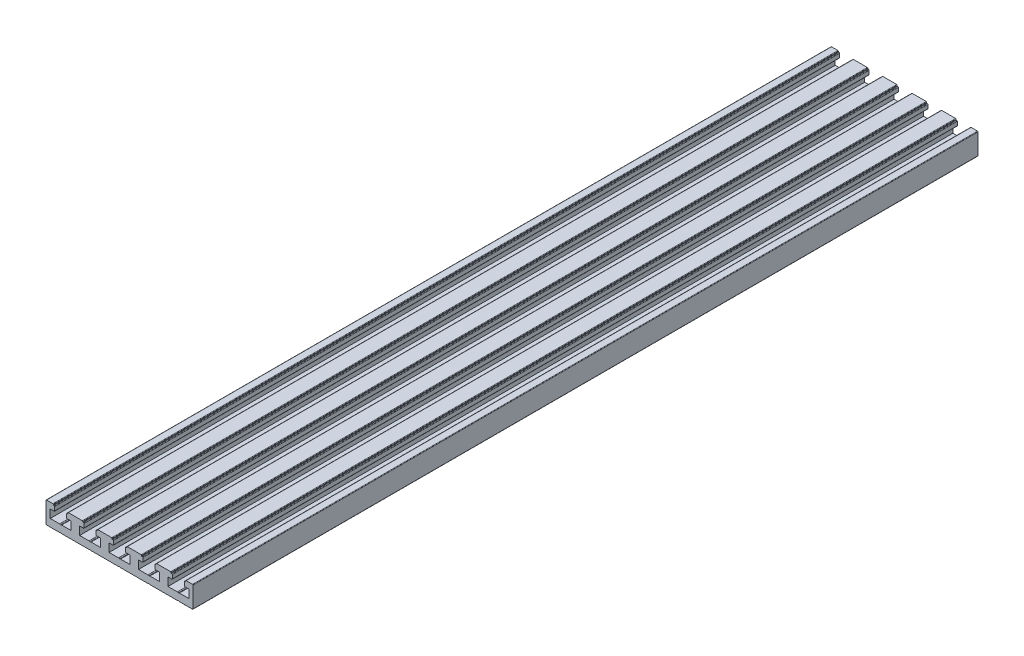
SolidWorks part; units mm, degrees
material "6061-T6 (SS)"
ref_plane "Front Plane" through (0, 0, 0) normal (0, 0, 1) x (1, 0, 0)
ref_plane "Top Plane" through (0, 0, 0) normal (0, 1, 0) x (1, 0, 0)
ref_plane "Right Plane" through (0, 0, 0) normal (1, 0, 0) x (0, 0, -1)
sketch "Sketch1" plane through (0, 0, 0) normal (0, 0, -1) x (-1, 0, 0)
  line L0 (0, 1.72) -> (0, -1.72) construction
  line L1 (-37.45, 8.85) -> (-37.45, -1.65)
  line L2 (-37.2, -1.9) -> (-30.5436, -1.9)
  line L3 (-30.4589, -1.8852) -> (-30, -1.72)
  line L4 (-30, -1.72) -> (-29.5411, -1.8852)
  line L5 (-29.4564, -1.9) -> (-15.5436, -1.9)
  line L6 (-15.4589, -1.8852) -> (-15, -1.72)
  line L7 (-15, -1.72) -> (-14.5411, -1.8852)
  line L8 (-14.4564, -1.9) -> (-0.5436, -1.9)
  line L9 (-0.4589, -1.8852) -> (0, -1.72)
  line L10 (0, -1.72) -> (0.4589, -1.8852)
  line L11 (0.5436, -1.9) -> (14.4564, -1.9)
  line L12 (14.5411, -1.8852) -> (15, -1.72)
  line L13 (15, -1.72) -> (15.4589, -1.8852)
  line L14 (15.5436, -1.9) -> (29.4564, -1.9)
  line L15 (29.5411, -1.8852) -> (30, -1.72)
  line L16 (30, -1.72) -> (30.4589, -1.8852)
  line L17 (30.5436, -1.9) -> (37.2, -1.9)
  line L18 (37.45, -1.65) -> (37.45, 8.85)
  line L19 (37.2, 9.1) -> (33.95, 9.1)
  line L20 (33.7, 8.85) -> (33.7, 8.5)
  line L21 (33.7, 8.5) -> (33.32, 8.5)
  line L22 (33.07, 8.25) -> (33.07, 6.35)
  line L23 (33.32, 6.1) -> (35.3, 6.1)
  line L24 (35.3, 6.1) -> (35.3, 1.9)
  line L25 (35.3, 1.9) -> (30.5436, 1.9)
  line L26 (30.4589, 1.8852) -> (30, 1.72)
  line L27 (30, 1.72) -> (29.5411, 1.8852)
  line L28 (29.4564, 1.9) -> (24.7, 1.9)
  line L29 (24.7, 1.9) -> (24.7, 6.1)
  line L30 (24.7, 6.1) -> (26.68, 6.1)
  line L31 (26.93, 6.35) -> (26.93, 8.25)
  line L32 (26.68, 8.5) -> (26.3, 8.5)
  line L33 (26.3, 8.5) -> (26.3, 8.85)
  line L34 (26.05, 9.1) -> (18.95, 9.1)
  line L35 (18.7, 8.85) -> (18.7, 8.5)
  line L36 (18.7, 8.5) -> (18.32, 8.5)
  line L37 (18.07, 8.25) -> (18.07, 6.35)
  line L38 (18.32, 6.1) -> (20.3, 6.1)
  line L39 (20.3, 6.1) -> (20.3, 1.9)
  line L40 (20.3, 1.9) -> (15.5436, 1.9)
  line L41 (15.4589, 1.8852) -> (15, 1.72)
  line L42 (15, 1.72) -> (14.5411, 1.8852)
  line L43 (14.4564, 1.9) -> (9.7, 1.9)
  line L44 (9.7, 1.9) -> (9.7, 6.1)
  line L45 (9.7, 6.1) -> (11.68, 6.1)
  line L46 (11.93, 6.35) -> (11.93, 8.25)
  line L47 (11.68, 8.5) -> (11.3, 8.5)
  line L48 (11.3, 8.5) -> (11.3, 8.85)
  line L49 (11.05, 9.1) -> (3.95, 9.1)
  line L50 (3.7, 8.85) -> (3.7, 8.5)
  line L51 (3.7, 8.5) -> (3.32, 8.5)
  line L52 (3.07, 8.25) -> (3.07, 6.35)
  line L53 (3.32, 6.1) -> (5.3, 6.1)
  line L54 (5.3, 6.1) -> (5.3, 1.9)
  line L55 (5.3, 1.9) -> (0.5436, 1.9)
  line L56 (0.4589, 1.8852) -> (0, 1.72)
  line L57 (0, 1.72) -> (-0.4589, 1.8852)
  line L58 (-0.5436, 1.9) -> (-5.3, 1.9)
  line L59 (-5.3, 1.9) -> (-5.3, 6.1)
  line L60 (-5.3, 6.1) -> (-3.32, 6.1)
  line L61 (-3.07, 6.35) -> (-3.07, 8.25)
  line L62 (-3.32, 8.5) -> (-3.7, 8.5)
  line L63 (-3.7, 8.5) -> (-3.7, 8.85)
  line L64 (-3.95, 9.1) -> (-11.05, 9.1)
  line L65 (-11.3, 8.85) -> (-11.3, 8.5)
  line L66 (-11.3, 8.5) -> (-11.68, 8.5)
  line L67 (-11.93, 8.25) -> (-11.93, 6.35)
  line L68 (-11.68, 6.1) -> (-9.7, 6.1)
  line L69 (-9.7, 6.1) -> (-9.7, 1.9)
  line L70 (-9.7, 1.9) -> (-14.4564, 1.9)
  line L71 (-14.5411, 1.8852) -> (-15, 1.72)
  line L72 (-15, 1.72) -> (-15.4589, 1.8852)
  line L73 (-15.5436, 1.9) -> (-20.3, 1.9)
  line L74 (-20.3, 1.9) -> (-20.3, 6.1)
  line L75 (-20.3, 6.1) -> (-18.32, 6.1)
  line L76 (-18.07, 6.35) -> (-18.07, 8.25)
  line L77 (-18.32, 8.5) -> (-18.7, 8.5)
  line L78 (-18.7, 8.5) -> (-18.7, 8.85)
  line L79 (-18.95, 9.1) -> (-26.05, 9.1)
  line L80 (-26.3, 8.85) -> (-26.3, 8.5)
  line L81 (-26.3, 8.5) -> (-26.68, 8.5)
  line L82 (-26.93, 8.25) -> (-26.93, 6.35)
  line L83 (-26.68, 6.1) -> (-24.7, 6.1)
  line L84 (-24.7, 6.1) -> (-24.7, 1.9)
  line L85 (-24.7, 1.9) -> (-29.4564, 1.9)
  line L86 (-29.5411, 1.8852) -> (-30, 1.72)
  line L87 (-30, 1.72) -> (-30.4589, 1.8852)
  line L88 (-30.5436, 1.9) -> (-35.3, 1.9)
  line L89 (-35.3, 1.9) -> (-35.3, 6.1)
  line L90 (-35.3, 6.1) -> (-33.32, 6.1)
  line L91 (-33.07, 6.35) -> (-33.07, 8.25)
  line L92 (-33.32, 8.5) -> (-33.7, 8.5)
  line L93 (-33.7, 8.5) -> (-33.7, 8.85)
  line L94 (-33.95, 9.1) -> (-37.2, 9.1)
  arc A0 (-37.45, -1.65) -> (-37.2, -1.9) centre (-37.2, -1.65) ccw
  arc A1 (-30.5436, -1.9) -> (-30.4589, -1.8852) centre (-30.5436, -1.65) ccw
  arc A2 (-29.5411, -1.8852) -> (-29.4564, -1.9) centre (-29.4564, -1.65) ccw
  arc A3 (-15.5436, -1.9) -> (-15.4589, -1.8852) centre (-15.5436, -1.65) ccw
  arc A4 (-14.5411, -1.8852) -> (-14.4564, -1.9) centre (-14.4564, -1.65) ccw
  arc A5 (-0.5436, -1.9) -> (-0.4589, -1.8852) centre (-0.5436, -1.65) ccw
  arc A6 (0.4589, -1.8852) -> (0.5436, -1.9) centre (0.5436, -1.65) ccw
  arc A7 (14.4564, -1.9) -> (14.5411, -1.8852) centre (14.4564, -1.65) ccw
  arc A8 (15.4589, -1.8852) -> (15.5436, -1.9) centre (15.5436, -1.65) ccw
  arc A9 (29.4564, -1.9) -> (29.5411, -1.8852) centre (29.4564, -1.65) ccw
  arc A10 (30.4589, -1.8852) -> (30.5436, -1.9) centre (30.5436, -1.65) ccw
  arc A11 (37.2, -1.9) -> (37.45, -1.65) centre (37.2, -1.65) ccw
  arc A12 (37.45, 8.85) -> (37.2, 9.1) centre (37.2, 8.85) ccw
  arc A13 (33.95, 9.1) -> (33.7, 8.85) centre (33.95, 8.85) ccw
  arc A14 (33.32, 8.5) -> (33.07, 8.25) centre (33.32, 8.25) ccw
  arc A15 (33.07, 6.35) -> (33.32, 6.1) centre (33.32, 6.35) ccw
  arc A16 (30.5436, 1.9) -> (30.4589, 1.8852) centre (30.5436, 1.65) ccw
  arc A17 (29.5411, 1.8852) -> (29.4564, 1.9) centre (29.4564, 1.65) ccw
  arc A18 (26.68, 6.1) -> (26.93, 6.35) centre (26.68, 6.35) ccw
  arc A19 (26.93, 8.25) -> (26.68, 8.5) centre (26.68, 8.25) ccw
  arc A20 (26.3, 8.85) -> (26.05, 9.1) centre (26.05, 8.85) ccw
  arc A21 (18.95, 9.1) -> (18.7, 8.85) centre (18.95, 8.85) ccw
  arc A22 (18.32, 8.5) -> (18.07, 8.25) centre (18.32, 8.25) ccw
  arc A23 (18.07, 6.35) -> (18.32, 6.1) centre (18.32, 6.35) ccw
  arc A24 (15.5436, 1.9) -> (15.4589, 1.8852) centre (15.5436, 1.65) ccw
  arc A25 (14.5411, 1.8852) -> (14.4564, 1.9) centre (14.4564, 1.65) ccw
  arc A26 (11.68, 6.1) -> (11.93, 6.35) centre (11.68, 6.35) ccw
  arc A27 (11.93, 8.25) -> (11.68, 8.5) centre (11.68, 8.25) ccw
  arc A28 (11.3, 8.85) -> (11.05, 9.1) centre (11.05, 8.85) ccw
  arc A29 (3.95, 9.1) -> (3.7, 8.85) centre (3.95, 8.85) ccw
  arc A30 (3.32, 8.5) -> (3.07, 8.25) centre (3.32, 8.25) ccw
  arc A31 (3.07, 6.35) -> (3.32, 6.1) centre (3.32, 6.35) ccw
  arc A32 (0.5436, 1.9) -> (0.4589, 1.8852) centre (0.5436, 1.65) ccw
  arc A33 (-0.4589, 1.8852) -> (-0.5436, 1.9) centre (-0.5436, 1.65) ccw
  arc A34 (-3.32, 6.1) -> (-3.07, 6.35) centre (-3.32, 6.35) ccw
  arc A35 (-3.07, 8.25) -> (-3.32, 8.5) centre (-3.32, 8.25) ccw
  arc A36 (-3.7, 8.85) -> (-3.95, 9.1) centre (-3.95, 8.85) ccw
  arc A37 (-11.05, 9.1) -> (-11.3, 8.85) centre (-11.05, 8.85) ccw
  arc A38 (-11.68, 8.5) -> (-11.93, 8.25) centre (-11.68, 8.25) ccw
  arc A39 (-11.93, 6.35) -> (-11.68, 6.1) centre (-11.68, 6.35) ccw
  arc A40 (-14.4564, 1.9) -> (-14.5411, 1.8852) centre (-14.4564, 1.65) ccw
  arc A41 (-15.4589, 1.8852) -> (-15.5436, 1.9) centre (-15.5436, 1.65) ccw
  arc A42 (-18.32, 6.1) -> (-18.07, 6.35) centre (-18.32, 6.35) ccw
  arc A43 (-18.07, 8.25) -> (-18.32, 8.5) centre (-18.32, 8.25) ccw
  arc A44 (-18.7, 8.85) -> (-18.95, 9.1) centre (-18.95, 8.85) ccw
  arc A45 (-26.05, 9.1) -> (-26.3, 8.85) centre (-26.05, 8.85) ccw
  arc A46 (-26.68, 8.5) -> (-26.93, 8.25) centre (-26.68, 8.25) ccw
  arc A47 (-26.93, 6.35) -> (-26.68, 6.1) centre (-26.68, 6.35) ccw
  arc A48 (-29.4564, 1.9) -> (-29.5411, 1.8852) centre (-29.4564, 1.65) ccw
  arc A49 (-30.4589, 1.8852) -> (-30.5436, 1.9) centre (-30.5436, 1.65) ccw
  arc A50 (-33.32, 6.1) -> (-33.07, 6.35) centre (-33.32, 6.35) ccw
  arc A51 (-33.07, 8.25) -> (-33.32, 8.5) centre (-33.32, 8.25) ccw
  arc A52 (-33.7, 8.85) -> (-33.95, 9.1) centre (-33.95, 8.85) ccw
  arc A53 (-37.2, 9.1) -> (-37.45, 8.85) centre (-37.2, 8.85) ccw
  point P2 (0, 0)
  dimension "D1" = 11
  dimension "D2" = 74.9
extrude "RawPart" add sketch "Sketch1" against normal blind 400
hole_wizard "CSK for M3 Flat Head Machine Screw1" positions "3DSketch1" profile "Sketch2" countersink size "M3" standard "ANSI Metric" end condition through all
sketch3d "3DSketch1"
  point P0 (-30, 1.9, 65)
  point P2 (30, 1.9, 65)
  point P35 (30, 1.9, 330)
  point P37 (-30, 1.9, 330)
  dimension "D1" = 65
  dimension "D2" = 7.45
  dimension "D3" = 60
  dimension "D4" = 330
sketch "Sketch2" plane through (-30, 1.9, 65) normal (1, 0, 0) x (0, 0, 1)
  line L0 (0, 0) -> (0, 3.8)
  line L1 (0, 3.8) -> (1.6, 3.8)
  line L2 (1.6, 3.8) -> (1.6, 1.4)
  line L3 (1.6, 1.4) -> (3, 0)
  line L5 (3, 0) -> (0, 0)
  line L6 (-1.6, 1.4) -> (-3, 0) construction
  line L11 (0, -6.35) -> (0, 107.95) construction
  dimension "Thru Hole Dia." = 3.2
  dimension "Thru Hole Depth" = 3.8
  dimension "Near C'Sink Dia." = 6
  dimension "Near C'Sink Angle" = 90
hole_wizard "M4x0.7 Tapped Hole1" positions "Sketch4" profile "Sketch5" tap size "M4x0.7" standard "ANSI Metric" end condition through all
sketch "Sketch4" plane through (0, 1.9, 0) normal (0, 1, 0) x (1, 0, 0)
  line L1 (-0.5436, 0) -> (-14.4564, 0) construction
  line L2 (-37.45, -400) -> (-37.45, 0) construction
  line L3 (15, -400) -> (15, 0) construction
  line L5 (-26.05, 0) -> (-18.95, 0) construction
  point P0 (15, -30)
  point P15 (15, -371)
  dimension "D1" = 30
  dimension "D2" = 52.45
  dimension "D3" = 371
sketch "Sketch5" plane through (15, 1.9, 30) normal (1, 0, 0) x (0, 0, 1)
  line L0 (0, 0) -> (0, 3.8)
  line L1 (0, 3.8) -> (1.65, 3.8)
  line L2 (1.65, 3.8) -> (1.65, 0)
  line L5 (1.65, 0) -> (0, 0)
  line L11 (0, -6.35) -> (0, 107.95) construction
  dimension "Thru Tap Drill Dia." = 3.3
  dimension "Thru Tap Drill Depth" = 3.8
cosmetic thread "Hole Thread4" parameters "D2"=4
cosmetic thread "Hole Thread7" parameters "D2"=4
sketch "Sketch6" [suppressed] plane through (0, 0, 0) normal (0, 0, -1) x (-1, 0, 0)
  line L1 (-14.5411, -9.9057) -> (-41.3903, -9.9057)
  line L2 (-14.5411, -9.9057) -> (-14.5411, 14.5956)
  line L3 (-14.5411, 14.5956) -> (-41.3903, 14.5956)
  line L4 (-41.3903, -9.9057) -> (-41.3903, 14.5956)
extrude "Cut-Extrude1" [suppressed] cut sketch "Sketch6" against normal through all
equation "\"D4@3DSketch1\"=\"D1@RawPart\"-\"D1@3DSketch1\"-5"
